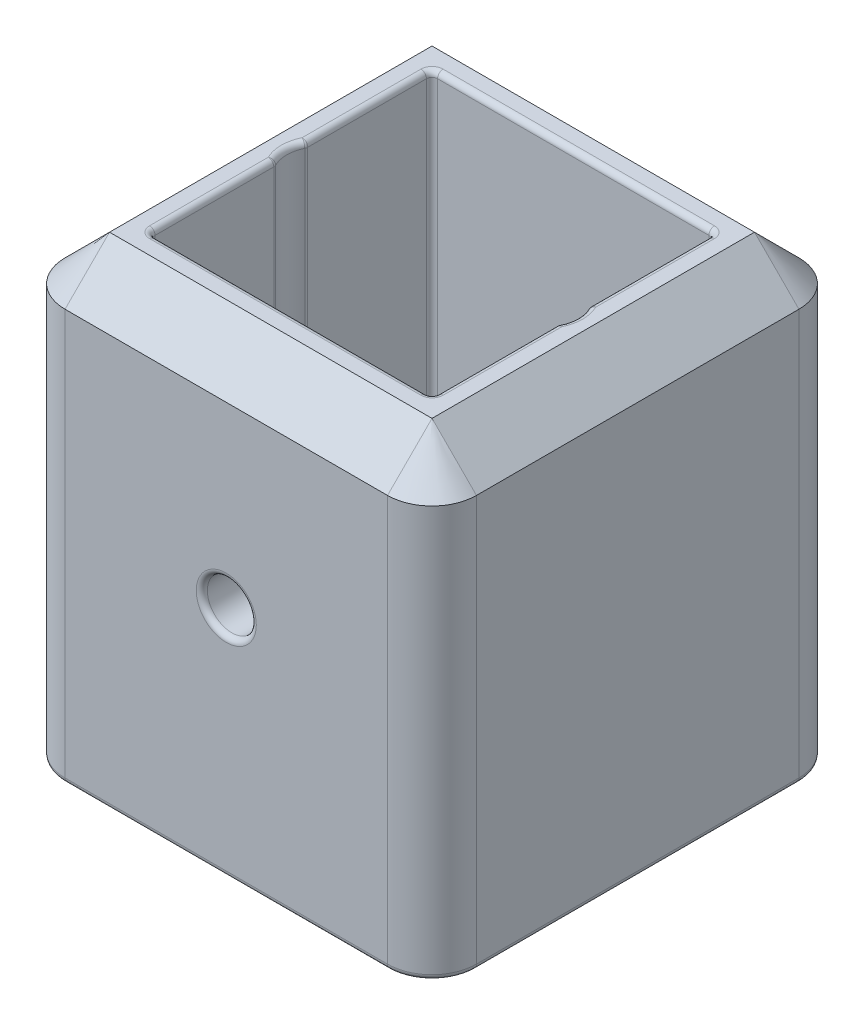
SolidWorks part; units mm, degrees
ref_plane "Ebene vorne" through (0, 0, 0) normal (0, 0, 1) x (1, 0, 0)
ref_plane "Ebene oben" through (0, 0, 0) normal (0, 1, 0) x (1, 0, 0)
ref_plane "Ebene rechts" through (0, 0, 0) normal (1, 0, 0) x (0, 0, -1)
sketch "Skizze1" plane through (0, 0, 0) normal (0, 1, 0) x (1, 0, 0)
  line L1 (-18.5, 18.5) -> (18.5, 18.5)
  line L2 (-18.5, 18.5) -> (-18.5, -18.5)
  line L3 (-18.5, -18.5) -> (18.5, -18.5)
  line L4 (18.5, 18.5) -> (18.5, -18.5)
  line L5 (-18.5, 18.5) -> (18.5, -18.5) construction
  line L6 (-18.5, -18.5) -> (18.5, 18.5) construction
  line L10 (0, 0) -> (10.25, 0) construction
  circle A0 centre (10.25, 0) radius 1.7
  circle A1 centre (5.125, -8.8768) radius 1.7
  circle A2 centre (-5.125, -8.8768) radius 1.7
  circle A3 centre (-10.25, 0) radius 1.7
  circle A4 centre (-5.125, 8.8768) radius 1.7
  circle A5 centre (5.125, 8.8768) radius 1.7
  circle A6 centre (0, 0) radius 5.5
  point P0 (0, 0)
  point P26 (0, 0)
  dimension "D3" = 10.25
  dimension "D4" = 3.4
  dimension "D1" = 37
  dimension "D5" = 6
extrude "Aufsatz-Linear austragen1" add sketch "Skizze1" against normal blind 6 contours L1 L4 L3 L2 | A3 | A4 | A5 | A0 | A2 | A1
ref_plane "Ebene1" through (0, 0, 0) normal (0, 1, 0) x (1, 0, 0)
sketch "Skizze2" plane through (0, 0, 0) normal (0, 1, 0) x (1, 0, 0)
  line L0 (12.7, 12.7) -> (7.5926, 12.7)
  line L1 (-12.7, 12.7) -> (-12.7, 3.9055)
  line L2 (-12.7, -12.7) -> (-7.5926, -12.7)
  line L3 (12.7, -12.7) -> (12.7, -3.9055)
  line L4 (-18.5, 18.5) -> (-18.5, -18.5)
  line L5 (-18.5, -18.5) -> (18.5, -18.5)
  line L6 (18.5, -18.5) -> (18.5, 18.5)
  line L7 (18.5, 18.5) -> (-18.5, 18.5)
  line L8 (-18.5, 18.5) -> (-18.5, -18.5)
  line L9 (-18.5, -18.5) -> (18.5, -18.5)
  line L10 (18.5, -18.5) -> (18.5, 18.5)
  line L11 (18.5, 18.5) -> (-18.5, 18.5)
  line L12 (-12.7, 3.9055) -> (-12.7, 1.4062)
  line L13 (-12.7, 12.7) -> (-12.7, -12.7) construction
  line L14 (-2.6574, 12.7) -> (-12.7, 12.7)
  line L15 (12.7, 12.7) -> (-12.7, 12.7) construction
  line L16 (7.5926, 12.7) -> (-2.6574, 12.7)
  line L17 (12.7, -3.9055) -> (12.7, -1.4062)
  line L18 (12.7, -12.7) -> (12.7, 12.7) construction
  line L19 (-7.5926, -12.7) -> (12.7, -12.7)
  line L20 (-12.7, -12.7) -> (12.7, -12.7) construction
  line L21 (-12.7, -1.4062) -> (-12.7, -12.7)
  line L23 (12.7, 1.4062) -> (12.7, 12.7)
  circle A1 centre (-5.125, -8.8768) radius 1.7 construction
  circle A2 centre (5.125, -8.8768) radius 1.7 construction
  circle A4 centre (5.125, 8.8768) radius 1.7 construction
  circle A5 centre (-5.125, 8.8768) radius 1.7 construction
  circle A7 centre (-5.125, -8.8768) radius 1.7 construction
  circle A8 centre (5.125, -8.8768) radius 1.7 construction
  circle A10 centre (5.125, 8.8768) radius 1.7 construction
  circle A11 centre (-5.125, 8.8768) radius 1.7 construction
  arc A18 (-12.7, 1.4062) -> (-12.7, -1.4062) centre (-10.05, 0) ccw
  arc A19 (12.7, -1.4062) -> (12.7, 1.4062) centre (10.05, 0) ccw
  dimension "D1" = 0
extrude "Aufsatz-Linear austragen2" add sketch "Skizze2" along normal blind 35
fillet "Verrundung1" radius 4 4 edges at (-18.5, 14.5, 18.5) (18.5, 14.5, 18.5) (-18.5, 14.5, -18.5) (18.5, 14.5, -18.5)
fillet "Verrundung4" radius 0.5 20 edges at (10.25, 0, 1.7) (5.125, 0, 10.5768) (-5.125, 0, 10.5768) (5.125, 0, -7.1768) (-5.125, 0, -7.1768) (-10.25, 0, 1.7) (-17.3284, -6, -17.3284) (-17.3284, -6, 17.3284) (17.3284, -6, 17.3284) (17.3284, -6, -17.3284) (5.125, -6, 10.5768) (-5.125, -6, 10.5768) (10.25, -6, 1.7) (5.125, -6, -7.1768) (-10.25, -6, 1.7) (-18.5, -6, 0) (0, -6, 18.5) (18.5, -6, 0) (0, -6, -18.5) (-5.125, -6, -7.1768)
fillet "Verrundung5" radius 0.5 24 edges at (12.7, 0, 7.0531) (-12.7, 0, 7.0531) (13.05, 0, 0) (-13.05, 0, 0) (-12.7, 35, -7.0531) (-13.05, 35, 0) (-12.7, 35, 7.0531) (0, 35, 12.7) (12.7, 35, 7.0531) (13.05, 35, 0) (12.7, 35, -7.0531) (0, 35, -12.7) (0, 0, 12.7) (12.7, 0, -7.0531) (0, 0, -12.7) (-12.7, 0, -7.0531) (12.7, 17.5, -1.4062) (12.7, 17.5, 1.4062) (12.7, 17.5, 12.7) (-12.7, 17.5, 12.7) (-12.7, 17.5, 1.4062) (-12.7, 17.5, -1.4062) (12.7, 17.5, -12.7) (-12.7, 17.5, -12.7)
chamfer "Fase1" distance 4 angle 45 8 edges at (-17.3284, 35, -17.3284) (0, 35, -18.5) (17.3284, 35, -17.3284) (18.5, 35, 0) (17.3284, 35, 17.3284) (0, 35, 18.5) (-17.3284, 35, 17.3284) (-18.5, 35, 0)
hole_wizard "Ø4.4 (4.4) Durchmesser Bohrung1" positions "Skizze3" profile "Skizze4" hole size "Ø4.4" standard "DIN" end condition through all
sketch "Skizze3" plane through (0, 0, 18.5) normal (0, 0, 1) x (1, 0, 0)
  line L0 (-18.5, 0) -> (18.5, 0) construction
  line L1 (-18.5, 0) -> (18.5, 0) construction
  line L2 (0, 0) -> (0, 15) construction
  point P4 (0, 15)
  dimension "D1" = 15
sketch "Skizze4" plane through (0, 15, 18.5) normal (1, 0, 0) x (0, -1, 0)
  line L0 (0, 0) -> (0, 37)
  line L1 (0, 37) -> (2.2, 37)
  line L2 (2.2, 37) -> (2.2, 0)
  line L5 (2.2, 0) -> (0, 0)
  line L11 (0, -6.35) -> (0, 107.95) construction
  dimension "Bohrerdurchmesser" = 4.4
  dimension "Bohrungstiefe" = 37
fillet "Verrundung6" radius 0.5 4 edges at (2.2, 15, 18.5) (-2.2, 15, 12.7) (2.2, 15, -18.5) (2.2, 15, -12.7)
sketch "Skizze5" plane through (0, -6, 0) normal (0, -1, 0) x (1, 0, 0)
  circle A0 centre (0, 0) radius 5.5 construction
  circle A1 centre (0, 0) radius 5.5
extrude "Schnitt-Linear austragen1" cut sketch "Skizze5" against normal blind 2
